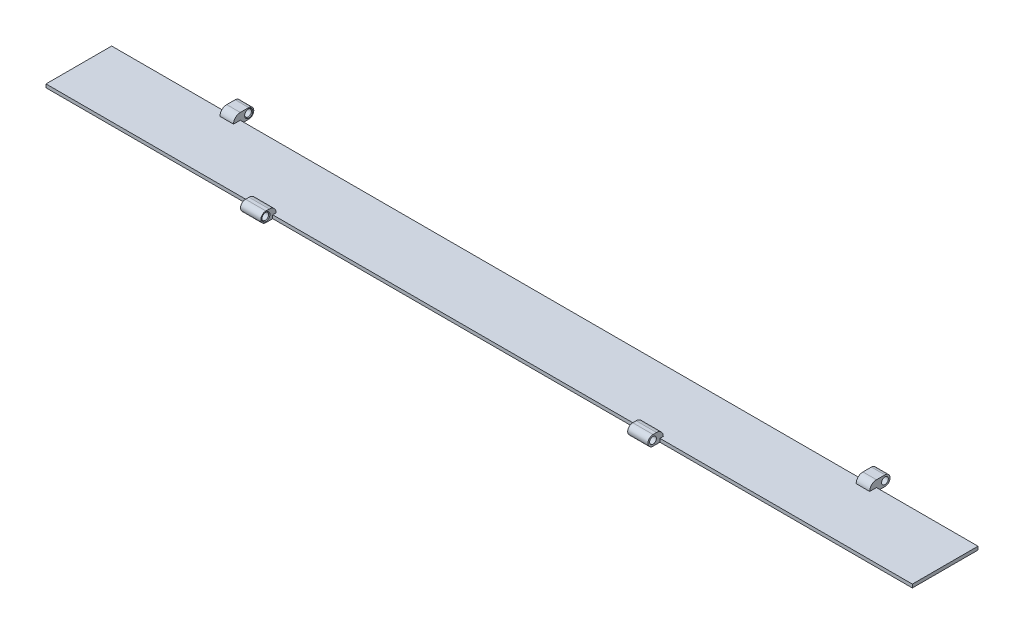
SolidWorks part; units mm, degrees
material "1.0037 (S235JR)"
ref_plane "Płaszczyzna przednia" through (0, 0, 0) normal (0, 0, 1) x (1, 0, 0)
ref_plane "Płaszczyzna górna" through (0, 0, 0) normal (0, 1, 0) x (1, 0, 0)
ref_plane "Płaszczyzna prawa" through (0, 0, 0) normal (1, 0, 0) x (0, 0, -1)
sketch "Szkic1" plane through (0, 0, 0) normal (0, 1, 0) x (1, 0, 0)
  line L1 (-640, -48.5) -> (640, -48.5)
  line L2 (-640, -48.5) -> (-640, 48.5)
  line L3 (-640, 48.5) -> (640, 48.5)
  line L4 (640, -48.5) -> (640, 48.5)
  line L5 (-640, -48.5) -> (640, 48.5) construction
  line L6 (-640, 48.5) -> (640, -48.5) construction
  point P0 (0, 0)
  dimension "D1" = 97
  dimension "D2" = 1280
extrude "Dodanie-wyciągnięcie1" add sketch "Szkic1" along normal blind 5
sketch "Szkic2" plane through (0, 5, 0) normal (0, 1, 0) x (1, 0, 0)
  line L0 (640, 48.5) -> (-640, 48.5) construction
  line L1 (-470, 68.5) -> (-450, 68.5)
  line L2 (-470, 68.5) -> (-470, 38.5)
  line L3 (-470, 38.5) -> (-450, 38.5)
  line L4 (-450, 68.5) -> (-450, 38.5)
  line L5 (-640, 48.5) -> (-640, -48.5) construction
  dimension "D1" = 20
  dimension "D2" = 10
  dimension "D3" = 20
  dimension "D4" = 170
extrude "Dodanie-wyciągnięcie2" add sketch "Szkic2" along normal blind 10 and the other way blind 5
fillet "Zaokrąglenie2" 2 edges at (-460, 0, -68.5) (-460, 15, -68.5) type full round first side face at (-230, 0, -29.25) second side face at (-460, 15, -53.5) middle face at (-460, 7.5, -68.5)
sketch "Szkic3" plane through (-470, 0, 0) normal (-1, 0, 0) x (0, 0, 1)
  circle A0 centre (-61, 7.5) radius 5
  dimension "D1" = 10
extrude "Wytnij-wyciągnięcie1" cut sketch "Szkic3" against normal up to next
sketch "Szkic4" plane through (0, 5, 0) normal (0, 1, 0) x (1, 0, 0)
  line L0 (-640, -48.5) -> (640, -48.5) construction
  line L1 (-335, -43.5) -> (-305, -43.5)
  line L2 (-335, -43.5) -> (-335, -66.15)
  line L3 (-335, -66.15) -> (-305, -66.15)
  line L4 (-305, -43.5) -> (-305, -66.15)
  line L5 (-640, 48.5) -> (-640, -48.5) construction
  dimension "D1" = 30
  dimension "D2" = 5
  dimension "D3" = 17.65
  dimension "D4" = 305
extrude "Dodanie-wyciągnięcie3" add sketch "Szkic4" along normal blind 10 and the other way blind 5
fillet "Zaokrąglenie3" radius 10 1 edges at (-460, 15, -38.5)
fillet "Zaokrąglenie4" 2 edges at (-320, 15, 66.15) (-320, 0, 66.15) type full round first side face at (-320, 15, 54.825) second side face at (-260, 0, 0.8583) middle face at (-320, 7.5, 66.15)
sketch "Szkic5" plane through (-335, 0, 0) normal (-1, 0, 0) x (0, 0, 1)
  circle A0 centre (58.65, 7.5) radius 5
  dimension "D1" = 10
extrude "Wytnij-wyciągnięcie2" cut sketch "Szkic5" against normal up to next
chamfer "Sfazowanie1" distance 1 angle 45 4 edges at (-305, 7.5, 53.65) (-335, 7.5, 63.65) (-450, 7.5, -66) (-470, 7.5, -56)
ref_plane "Płaszczyzna1" through (10, 0, 0) normal (1, 0, 0) x (0, 0, -1)
ref_plane "Płaszczyzna2" through (-34, 0, 0) normal (1, 0, 0) x (0, 0, -1)
fillet "Zaokrąglenie5" radius 10 1 edges at (-320, 15, 43.5)
mirror "Lustro2" about plane through (-34, 0, 0) normal (1, 0, 0) of "Zaokrąglenie5", "Wytnij-wyciągnięcie2", "Zaokrąglenie4", "Dodanie-wyciągnięcie3"
mirror "Lustro3" about plane through (10, 0, 0) normal (1, 0, 0) of "Wytnij-wyciągnięcie1", "Zaokrąglenie3", "Zaokrąglenie2", "Dodanie-wyciągnięcie2"
